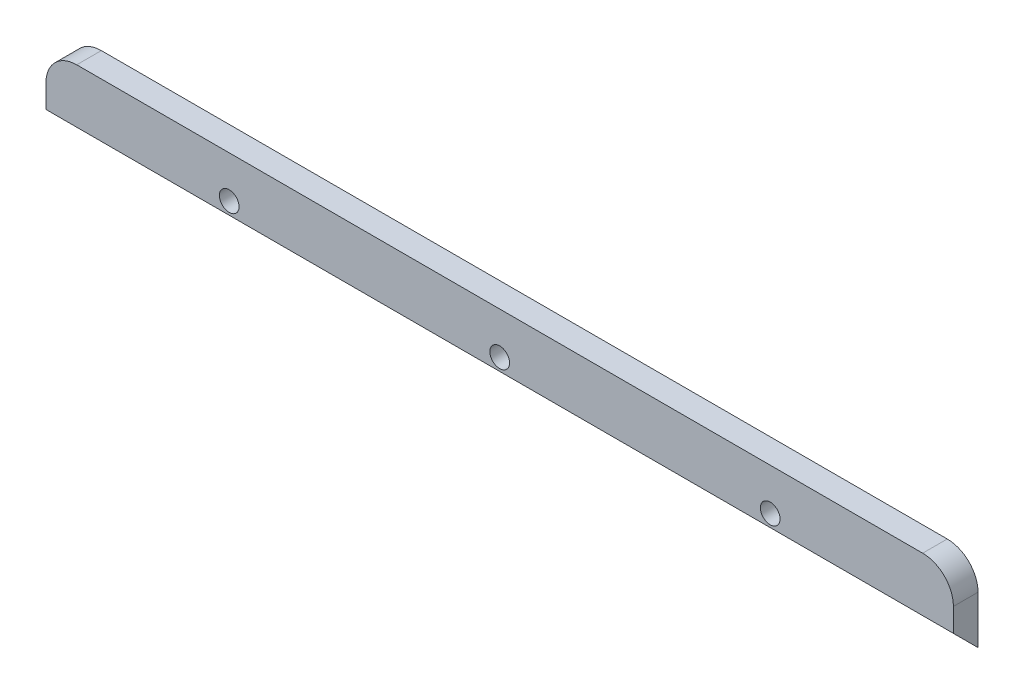
SolidWorks part; units mm, degrees
material "6061-T6 (SS)"
ref_plane "Front Plane" through (0, 0, 0) normal (0, 0, 1) x (1, 0, 0)
ref_plane "Top Plane" through (0, 0, 0) normal (0, 1, 0) x (1, 0, 0)
ref_plane "Right Plane" through (0, 0, 0) normal (1, 0, 0) x (0, 0, -1)
sketch "Sketch1" plane through (0, 0, 0) normal (1, 0, 0) x (0, 0, -1)
  line L0 (-3.0983, 0) -> (1.226, 0) construction
  line L1 (0, -3.2) -> (-2, -1.2)
  line L2 (0, -3.2) -> (0, 3.2)
  line L4 (-2, -1.2) -> (-2, 3.2)
  line L5 (-2, 3.2) -> (0, 3.2)
  dimension "D1" = 2
  dimension "D2" = 45
  dimension "D3" = 6.4
extrude "Boss-Extrude1" add sketch "Sketch1" along normal mid plane 73.8
sketch "Sketch4" [suppressed] plane through (0, 0, 0) normal (0, 0, 1) x (1, 0, 0)
  line L1 (7.5, 1.5) -> (-7.5, 1.5)
  line L2 (7.5, 1.5) -> (7.5, -3.2)
  line L3 (7.5, -3.2) -> (-7.5, -3.2)
  line L4 (-7.5, 1.5) -> (-7.5, -3.2)
  line L5 (0, 7.7759) -> (0, -8.8374) construction
  line L8 (-7.5, -3.2) -> (-7.5, 0.8) construction
  dimension "D1" = 4.7
hole_wizard "M2x0.4 Tapped Hole1" positions "Sketch2" profile "Sketch3" tap size "M2x0.4" standard "ANSI Metric" end condition through all
sketch "Sketch2" plane through (0, 0, 2) normal (0, 0, 1) x (1, 0, 0)
  circle A0 centre (-22, -0.2) radius 1.2
  circle A1 centre (-22, -0.2) radius 1.2 construction
  circle A2 centre (22, -0.2) radius 1.2
  circle A3 centre (22, -0.2) radius 1.2 construction
  point P0 (22, -0.2)
  point P2 (0, -0.2)
  point P5 (-22, -0.2)
sketch "Sketch3" plane through (22, -0.2, 2) normal (1, 0, 0) x (0, -1, 0)
  line L0 (0, 0) -> (0, 2)
  line L1 (0, 2) -> (0.8, 2)
  line L2 (0.8, 2) -> (0.8, 0)
  line L5 (0.8, 0) -> (0, 0)
  line L11 (0, -6.35) -> (0, 107.95) construction
  dimension "Thru Tap Drill Dia." = 1.6
  dimension "Thru Tap Drill Depth" = 2
cosmetic thread "Hole Thread1" parameters "D2"=2
cosmetic thread "Hole Thread2" parameters "D2"=2
cosmetic thread "Hole Thread3" parameters "D2"=2
extrude "Cut-Extrude4" [suppressed] cut sketch "Sketch4" along normal through all
fillet "Fillet3" radius 2.5 2 edges at (-36.9, 3.2, 1) (36.9, 3.2, 1)
